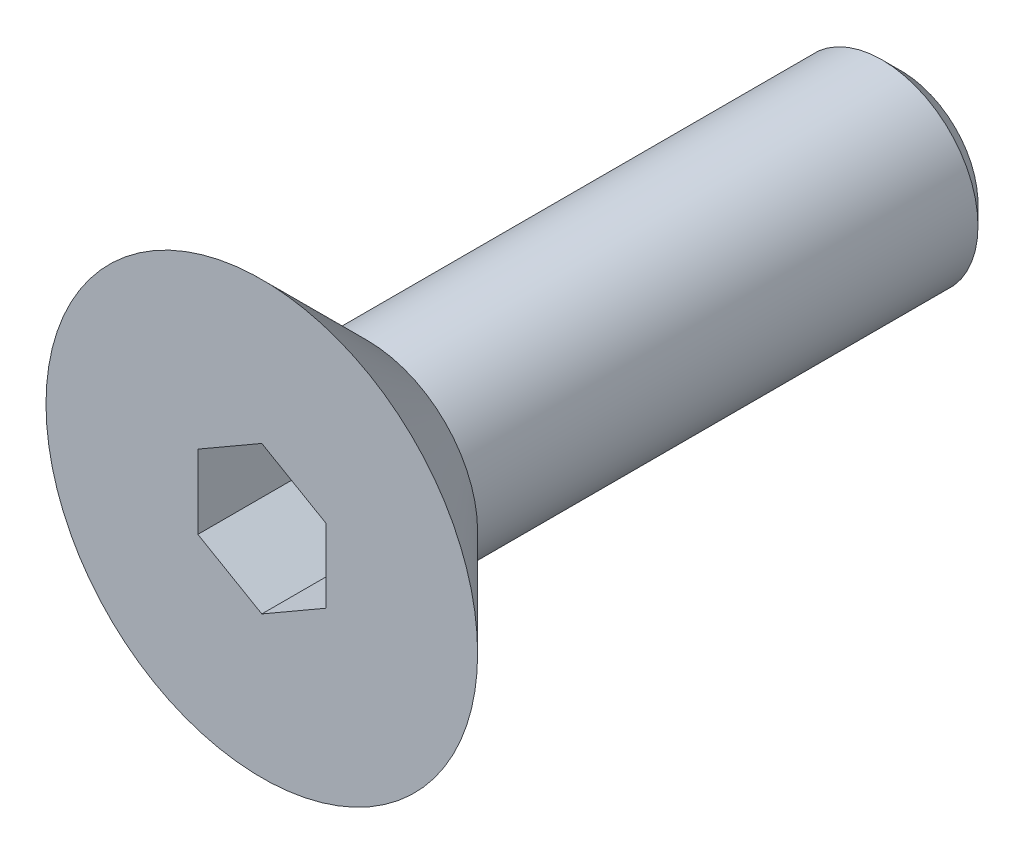
SolidWorks part; units mm, degrees
ref_plane "Front Plane" through (0, 0, 0) normal (0, 0, 1) x (1, 0, 0)
ref_plane "Top Plane" through (0, 0, 0) normal (0, 1, 0) x (1, 0, 0)
ref_plane "Right Plane" through (0, 0, 0) normal (1, 0, 0) x (0, 0, -1)
sketch "Sketch1" plane through (0, 0, 0) normal (0, 0, 1) x (1, 0, 0)
  circle A0 centre (0, 0) radius 3.375
  dimension "D1" = 6.75
extrude "Boss-Extrude1" add sketch "Sketch1" along normal blind 1.65
sketch "Sketch2" plane through (0, 0, 0) normal (0, 0, -1) x (-1, 0, 0)
  circle A0 centre (0, 0) radius 1.5
  dimension "D1" = 3
extrude "Boss-Extrude2" add sketch "Sketch2" along normal blind 8.35
chamfer "Chamfer1" distance 0.3 angle 45 1 edges at (-1.5, 0, -8.35)
sketch "Sketch3" plane through (0, 0, 1.65) normal (0, 0, 1) x (1, 0, 0)
  line L1 (0, 1.1547) -> (-1, 0.5774)
  line L2 (-1, 0.5774) -> (-1, -0.5774)
  line L3 (-1, -0.5774) -> (0, -1.1547)
  line L4 (0, -1.1547) -> (1, -0.5774)
  line L5 (1, -0.5774) -> (1, 0.5774)
  line L6 (1, 0.5774) -> (0, 1.1547)
  circle A0 centre (0, 0) radius 1 construction
  dimension "D1" = 2
extrude "Cut-Extrude1" cut sketch "Sketch3" against normal blind 2
chamfer "Chamfer2" distance 1.65 angle 45 1 edges at (3.375, 0, 0)
